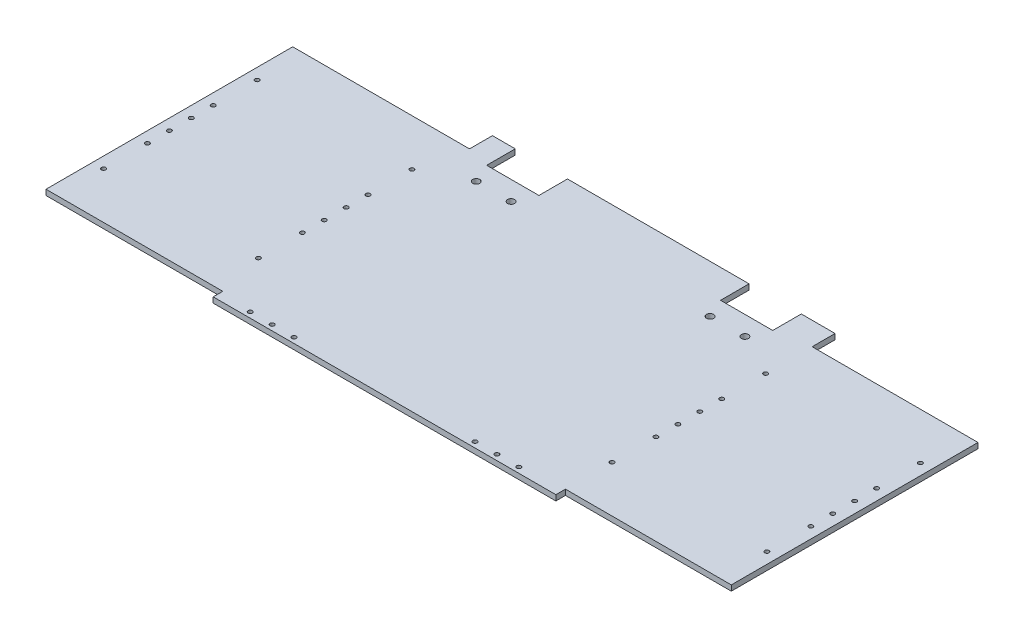
SolidWorks part; units mm, degrees
ref_plane "Front Plane" through (0, 0, 0) normal (0, 0, 1) x (1, 0, 0)
ref_plane "Top Plane" through (0, 0, 0) normal (0, 1, 0) x (1, 0, 0)
ref_plane "Right Plane" through (0, 0, 0) normal (1, 0, 0) x (0, 0, -1)
sketch "Sketch1" plane through (0, 0, 0) normal (0, 1, 0) x (1, 0, 0)
  line L0 (129, 0) -> (129, -7)
  line L1 (0, 0) -> (129, 0)
  line L2 (0, 0) -> (0, 180)
  line L3 (0, 180) -> (129, 180)
  line L4 (500, 0) -> (500, 180)
  line L5 (129, -7) -> (379, -7)
  line L6 (379, -7) -> (379, 0)
  line L7 (0, 90) -> (500, 90) construction
  line L8 (129, 180) -> (129, 196.718)
  line L9 (129, 196.718) -> (145.65, 196.718)
  line L10 (379, 196.718) -> (379, 180)
  line L11 (250, 195.398) -> (250, -38.1) construction
  line L12 (379, 0) -> (500, 0)
  line L13 (379, 180) -> (500, 180)
  line L14 (129, 161.92) -> (379, 161.92) construction
  line L15 (129, -3) -> (250, -3) construction
  line L16 (145.65, 196.718) -> (145.65, 175.89)
  line L17 (145.65, 175.89) -> (183.75, 175.89)
  line L18 (183.75, 175.89) -> (183.75, 196.718)
  line L19 (183.75, 196.718) -> (316.25, 196.718)
  line L20 (316.25, 175.89) -> (354.35, 175.89)
  line L21 (354.35, 196.718) -> (379, 196.718)
  line L23 (354.35, 196.718) -> (354.35, 175.89)
  line L24 (316.25, 175.89) -> (316.25, 196.718)
  circle A0 centre (152, 161.92) radius 2.564
  circle A1 centre (177.4, 161.92) radius 2.564
  circle A4 centre (152, -3) radius 1.55
  circle A5 centre (184, -3) radius 1.55
  circle A8 centre (322.6, 161.92) radius 2.564
  circle A9 centre (348, 161.92) radius 2.564
  circle A10 centre (168, -3) radius 1.55
  circle A11 centre (316, -3) radius 1.55
  circle A12 centre (332, -3) radius 1.55
  circle A13 centre (348, -3) radius 1.55
  circle A14 centre (121, 146) radius 1.55
  circle A15 centre (121, 114) radius 1.55
  circle A16 centre (121, 98) radius 1.55
  circle A17 centre (121, 82) radius 1.55
  circle A18 centre (121, 66) radius 1.55
  circle A19 centre (121, 34) radius 1.55
  circle A20 centre (379, 146) radius 1.55
  circle A21 centre (379, 114) radius 1.55
  circle A22 centre (379, 98) radius 1.55
  circle A23 centre (379, 82) radius 1.55
  circle A24 centre (379, 66) radius 1.55
  circle A25 centre (379, 34) radius 1.55
  circle A26 centre (8, 146) radius 1.55
  circle A27 centre (8, 114) radius 1.55
  circle A28 centre (8, 98) radius 1.55
  circle A29 centre (8, 82) radius 1.55
  circle A30 centre (8, 66) radius 1.55
  circle A31 centre (8, 34) radius 1.55
  circle A32 centre (492, 34) radius 1.55
  circle A33 centre (492, 66) radius 1.55
  circle A34 centre (492, 82) radius 1.55
  circle A35 centre (492, 98) radius 1.55
  circle A36 centre (492, 114) radius 1.55
  circle A37 centre (492, 146) radius 1.55
  point P10 (250, 90)
  dimension "D7" = 3.1
  dimension "D9" = 5.128
  dimension "D16" = 3.1
  dimension "D21" = 3.1
  dimension "D1" = 180
  dimension "D2" = 500
  dimension "D3" = 250
  dimension "D5" = 250
  dimension "D10" = 25.4
  dimension "D11" = 23
  dimension "D12" = 16
  dimension "D13" = 16
  dimension "D14" = 23
  dimension "D15" = 4
  dimension "D4" = 3
  dimension "D17" = 32
  dimension "D19" = 16
  dimension "D20" = 8
  dimension "D18" = 8
  dimension "D22" = 8
  dimension "D23" = 16
  dimension "D24" = 32
  dimension "D25" = 8
  dimension "D8" = 16.718
  dimension "D6" = 18.08
  dimension "D26" = 6.35
  dimension "D27" = 6.35
  dimension "D28" = 13.97
  dimension "D29" = 129
extrude "Boss-Extrude1" add sketch "Sketch1" along normal blind 4
equation "\"cf_tube_outer_diameter\"= 25mm"
equation "\"cf_tube_inner_diameter\" = 21mm"
equation "\"mid_plate_mid_to_top\" = 100mm"
equation "\"mid_plate_mid_to_bottom\" = 30mm"
equation "\"mid_plate_horizontal_spacing\"=250mm"
equation "\"cf_plate_thickness\" =4mm"
equation "\"mid_tube_length\" = 121mm"
equation "\"mid_plate_bottom_width\" = 180mm"
equation "\"D1@Sketch1\"=\"mid_plate_bottom_width\""
equation "\"D1@Boss-Extrude1\"=\"cf_plate_thickness\""
equation "\"D5@Sketch1\"=\"mid_plate_horizontal_spacing\""
equation "\"D3@Sketch1\"=\"mid_plate_horizontal_spacing\""
